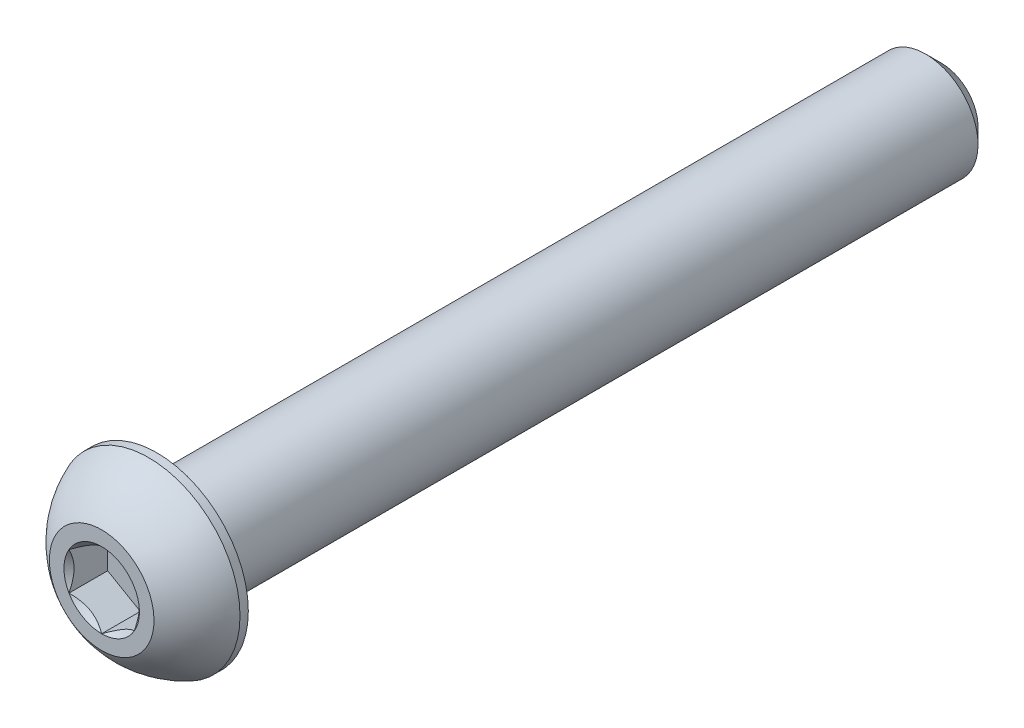
SolidWorks part; units mm, degrees
ref_plane "Front" through (0, 0, 0) normal (0, 0, 1) x (1, 0, 0)
ref_plane "Top" through (0, 0, 0) normal (0, 1, 0) x (1, 0, 0)
ref_plane "Right" through (0, 0, 0) normal (1, 0, 0) x (0, 0, -1)
sketch "Sketch1" plane through (0, 0, 0) normal (1, 0, 0) x (0, 0, -1)
  line L2 (3.3528, 3.175) -> (50.9778, 3.175)
  line L3 (50.9778, 3.175) -> (50.9778, 0)
  line L4 (50.9778, 0) -> (3.3528, 0)
  line L6 (2.8499, 5.5499) -> (3.3528, 5.5499) construction
  line L7 (50.9778, 3.175) -> (50.9778, -3.175) construction
  line L8 (0, 0) -> (3.3528, 0) construction
  line L9 (3.3528, 5.5499) -> (3.3528, -5.5499) construction
  line L11 (3.3528, 3.175) -> (3.3528, 0)
  line L13 (0, 1.9844) -> (0, -1.9844) construction
  line L14 (0, 1.9844) -> (0, 3.175) construction
  arc A3 (0, 3.175) -> (2.8499, 5.5499) centre (5.0603, 0) cw construction
  dimension "D1" = 0.5029
revolve "Revolve1" add sketch "Sketch1" angle 360 mid plane about L4
cosmetic thread "Cosmetic Thread1" parameters "D2"=4.8387
cosmetic thread "Cosmetic Thread2" parameters "D2"=4.8387
sketch "Sketch3" plane through (0, 0, -50.9778) normal (0, 0, -1) x (-1, 0, 0)
  circle A0 centre (0, 0) radius 3.175
curve "Helix/Spiral1" pitch 1.27 height 48.895 turns 38.5
sketch "Sketch2" plane through (0, 0, 0) normal (1, 0, 0) x (0, 0, -1)
  line L0 (50.9778, 3.175) -> (52.0891, 3.175)
  line L1 (52.0891, 3.175) -> (51.6128, 2.3501)
  line L2 (51.6128, 2.3501) -> (51.4541, 2.3501)
  line L3 (51.4541, 2.3501) -> (50.9778, 3.175)
  line L4 (51.2159, 2.7626) -> (51.8509, 2.7626) construction
  dimension "D1" = 60
  dimension "D2" = 0.1588
  dimension "D3" = 0.635
chamfer "Chamfer1" distance 0.9525 angle 45 1 edges at (0, 3.175, -50.9778)
sweep "Cut-Sweep1" [suppressed] cut profiles "Sketch2" path "Helix/Spiral1"
sketch "Sketch7" plane through (0, 0, 0) normal (1, 0, 0) x (0, 0, -1)
  line L6 (2.8499, 5.5499) -> (3.3528, 5.5499) construction
  line L8 (0, 0) -> (3.3528, 0) construction
  line L11 (3.3528, 5.5499) -> (3.3528, -5.5499) construction
  line L12 (2.8499, 5.5499) -> (3.3528, 5.5499)
  line L13 (0, 0) -> (3.3528, 0)
  line L14 (0, 1.9844) -> (0, -1.9844) construction
  line L15 (3.3528, 5.5499) -> (3.3528, 0)
  line L16 (0, 3.175) -> (0, 0)
  arc A2 (2.8499, 5.5499) -> (0, 3.175) centre (5.0603, 0) ccw construction
  arc A3 (2.8499, 5.5499) -> (0, 3.175) centre (5.0603, 0) ccw
revolve "Revolve2" add sketch "Sketch7" angle 360 mid plane about L13
sketch "Sketch5" plane through (0, 0, 0) normal (0, 0, 1) x (1, 0, 0)
  line L1 (1.9844, -1.1457) -> (1.9844, 1.1457)
  line L2 (1.9844, 1.1457) -> (0, 2.2914)
  line L3 (0, 2.2914) -> (-1.9844, 1.1457)
  line L4 (-1.9844, 1.1457) -> (-1.9844, -1.1457)
  line L5 (-1.9844, -1.1457) -> (0, -2.2914)
  line L6 (0, -2.2914) -> (1.9844, -1.1457)
  circle A0 centre (0, 0) radius 1.9844 construction
extrude "Cut-Extrude2" cut sketch "Sketch5" against normal blind 2.347
sketch "Sketch6" plane through (0, 0, 0) normal (0, 0, 1) x (1, 0, 0)
  circle A0 centre (0, 0) radius 2.2914
extrude "Cut-Extrude3" cut sketch "Sketch6" against normal blind 2.347 draft 45
sketch "Sketch9" [suppressed] plane through (0, 0, -3.3528) normal (0, 0, 1) x (1, 0, 0)
  circle A2 centre (0, 0) radius 3.175
extrude "Boss-Extrude2" [suppressed] add sketch "Sketch9" against normal offset from surface (25.4 mm away) 22.225
sketch "Sketch10" plane through (0, 0, 0) normal (1, 0, 0) x (0, 0, -1)
  line L0 (50.9778, 3.175) -> (50.9778, -3.175) construction
  point P0 (49.0728, -3.175)
  dimension "D1" = 1.905
equation "\"D3@Helix/Spiral1\" = \"Lg@Sketch1\" + \"D4@Helix/Spiral1\""
equation "\"D2@Sketch2\" = \"D4@Helix/Spiral1\" * .125"
equation "\"D3@Sketch2\" = \"D4@Helix/Spiral1\" * .5"
equation "\"D1@Chamfer1\" = \"D4@Helix/Spiral1\" * .75"
equation "\"D1@Cut-Extrude2\" = \"Head Ht@Sketch1\" * .7"
equation "\"D1@Sketch1\" = \"Head Ht@Sketch1\" * .15"
equation "\"D1@Sketch10\" = \"D4@Helix/Spiral1\" * 1.5"
equation "\"D1@Cut-Extrude3\" = \"D1@Cut-Extrude2\""
